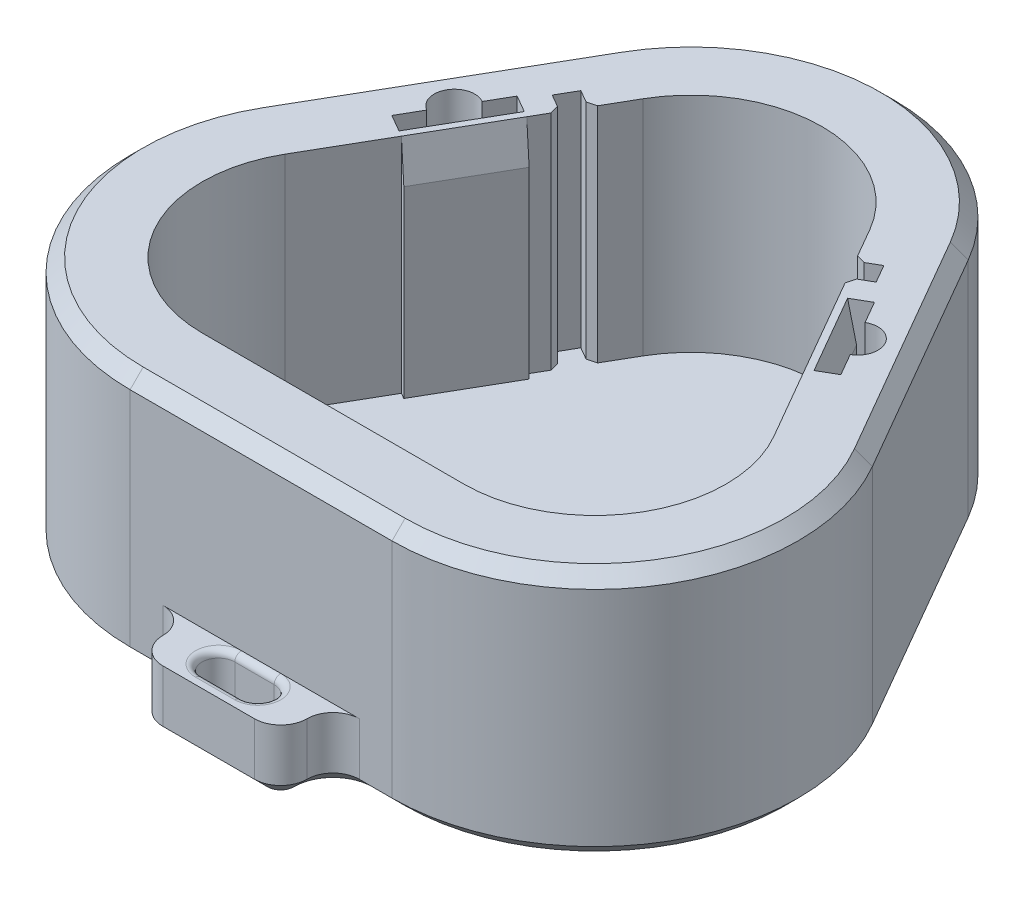
SolidWorks part; units mm, degrees
ref_plane "Front Plane" through (0, 0, 0) normal (0, 0, 1) x (1, 0, 0)
ref_plane "Top Plane" through (0, 0, 0) normal (0, 1, 0) x (1, 0, 0)
ref_plane "Right Plane" through (0, 0, 0) normal (1, 0, 0) x (0, 0, -1)
sketch "Sketch1" plane through (0, 0, 0) normal (0, 1, 0) x (1, 0, 0)
  line L0 (0, 11.5407) -> (-9.9945, -5.7703) construction
  line L1 (-9.9945, -5.7703) -> (9.9945, -5.7703) construction
  line L2 (9.9945, -5.7703) -> (0, 11.5407) construction
  line L3 (-9.9945, -5.7703) -> (4.9973, 2.8852) construction
  line L4 (-4.9973, 2.8852) -> (9.9945, -5.7703) construction
  line L5 (-8.6555, 16.5379) -> (-18.65, -0.7731)
  line L6 (-9.9945, -15.7648) -> (9.9945, -15.7648)
  line L7 (8.6555, 16.5379) -> (18.65, -0.7731)
  line L8 (0, 21.5352) -> (0, -15.7648) construction
  line L9 (-13.4186, 19.2879) -> (-23.4131, 1.9769)
  line L10 (-9.9945, -21.2648) -> (9.9945, -21.2648)
  line L11 (13.4186, 19.2879) -> (23.4131, 1.9769)
  line L12 (-11.9027, 10.9135) -> (-11.4697, 10.6635)
  line L13 (-11.4697, 10.6635) -> (-14.9697, 4.6013)
  line L14 (-14.9697, 4.6013) -> (-15.4027, 4.8513)
  line L15 (-15.4027, 4.8513) -> (-11.9027, 10.9135)
  line L16 (-13.2197, 7.6324) -> (-13.6527, 7.8824) construction
  line L21 (14.9697, 4.6013) -> (11.4697, 10.6635)
  line L22 (15.4027, 4.8513) -> (14.9697, 4.6013)
  line L23 (11.4697, 10.6635) -> (11.9027, 10.9135)
  line L24 (13.2197, 7.6324) -> (13.6527, 7.8824) construction
  line L25 (-3.5, -15.2648) -> (3.5, -15.2648)
  line L26 (-3.5, -15.7648) -> (-3.5, -15.2648)
  line L27 (3.5, -15.2648) -> (3.5, -15.7648)
  line L28 (0, -15.2648) -> (0, -15.7648) construction
  line L29 (-3.5, -15.7648) -> (3.5, -15.7648)
  line L30 (11.9027, 10.9135) -> (15.4027, 4.8513)
  line L34 (8.6555, 16.5379) -> (18.65, -0.7731) construction
  line L35 (-8.6555, 16.5379) -> (-18.65, -0.7731) construction
  line L36 (-10.176, 13.9044) -> (-11.5616, 14.7044)
  line L37 (-11.5616, 14.7044) -> (-12.3616, 13.3188)
  line L38 (-12.3616, 13.3188) -> (-10.976, 12.5188)
  line L39 (-10.976, 12.5188) -> (-10.176, 13.9044)
  line L40 (10.176, 13.9044) -> (11.5616, 14.7044)
  line L41 (11.5616, 14.7044) -> (12.3616, 13.3188)
  line L42 (12.3616, 13.3188) -> (10.976, 12.5188)
  line L43 (-12.7688, 11.4135) -> (-16.2688, 5.3513)
  line L44 (-16.2688, 5.3513) -> (-17.1348, 5.8513)
  line L45 (-17.1348, 5.8513) -> (-13.6348, 11.9135)
  line L46 (-13.6348, 11.9135) -> (-12.7688, 11.4135)
  line L47 (13.6348, 11.9135) -> (12.7688, 11.4135)
  line L48 (16.2688, 5.3513) -> (17.1348, 5.8513)
  line L49 (17.1348, 5.8513) -> (13.6348, 11.9135)
  line L50 (12.7688, 11.4135) -> (16.2688, 5.3513)
  line L51 (-13.0188, 10.9805) -> (-12.5858, 10.7305)
  line L52 (-12.5858, 10.7305) -> (-13.0858, 9.8645)
  line L53 (-13.0858, 9.8645) -> (-13.5188, 10.1145)
  line L54 (-13.5188, 10.1145) -> (-13.0188, 10.9805)
  line L55 (-15.0858, 6.4004) -> (-15.5188, 6.6504)
  line L56 (-16.0188, 5.7843) -> (-15.5858, 5.5343)
  line L57 (-15.5858, 5.5343) -> (-15.0858, 6.4004)
  line L58 (16.0188, 5.7843) -> (15.5858, 5.5343)
  line L59 (15.5858, 5.5343) -> (15.0858, 6.4004)
  line L60 (15.0858, 6.4004) -> (15.5188, 6.6504)
  line L61 (12.5858, 10.7305) -> (13.0858, 9.8645)
  line L62 (13.0188, 10.9805) -> (12.5858, 10.7305)
  line L63 (13.0858, 9.8645) -> (13.5188, 10.1145)
  arc A1 (-18.65, -0.7731) -> (-9.9945, -15.7648) centre (-9.9945, -5.7703) ccw
  arc A2 (9.9945, -15.7648) -> (18.65, -0.7731) centre (9.9945, -5.7703) ccw
  arc A5 (8.6555, 16.5379) -> (-8.6555, 16.5379) centre (0, 11.5407) ccw
  arc A6 (13.4186, 19.2879) -> (-13.4186, 19.2879) centre (0, 11.5407) ccw
  arc A7 (-23.4131, 1.9769) -> (-9.9945, -21.2648) centre (-9.9945, -5.7703) ccw
  arc A8 (9.9945, -21.2648) -> (23.4131, 1.9769) centre (9.9945, -5.7703) ccw
  arc A9 (-14.6098, 10.2248) -> (-16.1598, 7.5401) centre (-15.3848, 8.8824) ccw
  arc A10 (14.6098, 10.2248) -> (16.1598, 7.5401) centre (15.3848, 8.8824) cw
  point P5 (0, 21.5352)
  point P7 (0, 0)
  point P32 (-13.6527, 7.8824)
  point P50 (0, 0)
  dimension "D1" = 37.3
  dimension "D2" = 5.5
  dimension "D8" = 3.1
  dimension "D3" = 7
  dimension "D4" = 0.5
  dimension "D5" = 1.6
  dimension "D7" = 3.0409
  dimension "D9" = 1
  dimension "D10" = 1.5
  dimension "D11" = 1
  dimension "D12" = 0.5
  dimension "D13" = 6
  dimension "D6" = 3
extrude "Boss-Extrude1" add sketch "Sketch1" along normal blind 17 contours L10 A8 L11 A6 L9 A7 A9 L45 L46 L43 L51 L52 L53 L55 L57 L56 L44 A5 L7 L40 L41 L42 L23 L21 L22 A2 L6 L27 L25 L26 A1 L5 L14 L13 L12 L38 L37 L36 L49 A10 | L53 L52 L51 L43 | L56 L57 L55 L43 | L61 L63 L50 L62 | L60 L59 L58 L50 | L14 L13 L12 L5 | L23 L21 L22 L7 region at (-13.4362, 0, -7.7574) region at (13.4362, 0, -7.7574) region at (0, 0, -26.3329) region at (-13.0523, 0, -10.4225) region at (-15.5523, 0, -6.0924) region at (13.0523, 0, -10.4225) region at (15.5523, 0, -6.0924)
chamfer "Chamfer1" distance 0.5 angle 45 4 edges at (10.176, 8.5, -13.9044) (-10.176, 8.5, -13.9044) (10.976, 8.5, -12.5188) (-10.976, 8.5, -12.5188) tangent propagation no
extrude "Cut-Extrude1" cut sketch "Sketch1<3>" along normal blind 13 contours L53 L52 L51 L43 | L56 L57 L55 L43 | L61 L63 L50 L62 | L60 L59 L58 L50 region at (-13.0523, 0, -10.4225) region at (-15.5523, 0, -6.0924) region at (13.0523, 0, -10.4225) region at (15.5523, 0, -6.0924)
sketch "Sketch1<3>" plane through (0, 0, 0) normal (0, 1, 0) x (1, 0, 0) same geometry as "Sketch1"
extrude "Boss-Extrude2" add sketch "Sketch1<4>" against normal blind 2 contours L11 A8 L10 A7 L9 A6
sketch "Sketch1<4>" plane through (0, 0, 0) normal (0, 1, 0) x (1, 0, 0) same geometry as "Sketch1"
sketch "Sketch2" plane through (0, -2, 0) normal (0, -1, 0) x (1, 0, 0)
  line L0 (5.5, 21.2648) -> (5.5, 25.2648)
  line L4 (-9.9945, 21.2648) -> (9.9945, 21.2648) construction
  line L5 (5.5, 25.2648) -> (-5.5, 25.2648)
  line L6 (-5.5, 25.2648) -> (-5.5, 21.2648)
  line L7 (-5.5, 21.2648) -> (5.5, 21.2648)
  line L8 (-1.5, 23.0148) -> (1.5, 23.0148) construction
  line L9 (-1.5, 24.2648) -> (1.5, 24.2648)
  line L10 (-1.5, 21.7648) -> (1.5, 21.7648)
  circle A0 centre (-15.3848, -8.8824) radius 1.55
  circle A1 centre (15.3848, -8.8824) radius 1.55
  arc A2 (14.6098, -10.2248) -> (16.1598, -7.5401) centre (15.3848, -8.8824) ccw construction
  arc A3 (-16.1598, -7.5401) -> (-14.6098, -10.2248) centre (-15.3848, -8.8824) ccw construction
  arc A6 (-1.5, 24.2648) -> (-1.5, 21.7648) centre (-1.5, 23.0148) ccw
  arc A7 (1.5, 21.7648) -> (1.5, 24.2648) centre (1.5, 23.0148) ccw
  circle A8 centre (0, 0) radius 2.5
  point P15 (0, 21.2648)
  point P18 (0, 25.2648)
  point P21 (0, 23.0148)
  line M12 (9.9945, 21.2648) -> (-9.9945, 21.2648)
  dimension "D4" = 5.5
  dimension "D6" = 5
  dimension "D1" = 11
  dimension "D2" = 4
  dimension "D3" = 2.5
  dimension "D5" = 0.5
extrude "Cut-Extrude2" cut sketch "Sketch2" against normal up to vertex (2 mm away) up to point (-16.1598, 0, -7.5401)
extrude "Boss-Extrude3" add sketch "Sketch2<2>" against normal blind 5 contours L5 L6 L0 A7 L10 A6 L9 M12 region at (0, -2, 21.3819)
sketch "Sketch2<2>" plane through (0, -2, 0) normal (0, -1, 0) x (1, 0, 0) same geometry as "Sketch2"
fillet "Fillet1" radius 2 4 edges at (5.5, 0.5, 21.2648) (5.5, 0.5, 25.2648) (-5.5, 0.5, 25.2648) (-5.5, 0.5, 21.2648)
fillet "Fillet2" radius 0.5 4 edges at (0, 3, 24.2648) (2.75, 3, 23.0148) (0, 3, 21.7648) (-2.75, 3, 23.0148)
chamfer "Chamfer3" distance 0.5 distance2 3 4 edges at (-14.5188, 17, -8.3824) (14.5188, 17, -8.3824) (13.2197, 17, -7.6324) (-13.2197, 17, -7.6324) first distance on face at (-15.3198, 17, -8.8449)
chamfer "Chamfer4" distance 1 angle 45 18 edges at (6.0858, -2, 21.8506) (8.7473, -2, 21.2648) (4.9142, -2, 24.679) (23.4131, -2, 13.5176) (0, -2, 25.2648) (18.4159, -2, -10.6324) (-4.9142, -2, 24.679) (0, -2, -27.0352) (-6.0858, -2, 21.8506) (-18.4159, -2, -10.6324) (-8.7473, -2, 21.2648) (-23.4131, -2, 13.5176) (18.4159, 17, -10.6324) (0, 17, -27.0352) (23.4131, 17, 13.5176) (-18.4159, 17, -10.6324) (0, 17, 21.2648) (-23.4131, 17, 13.5176)
